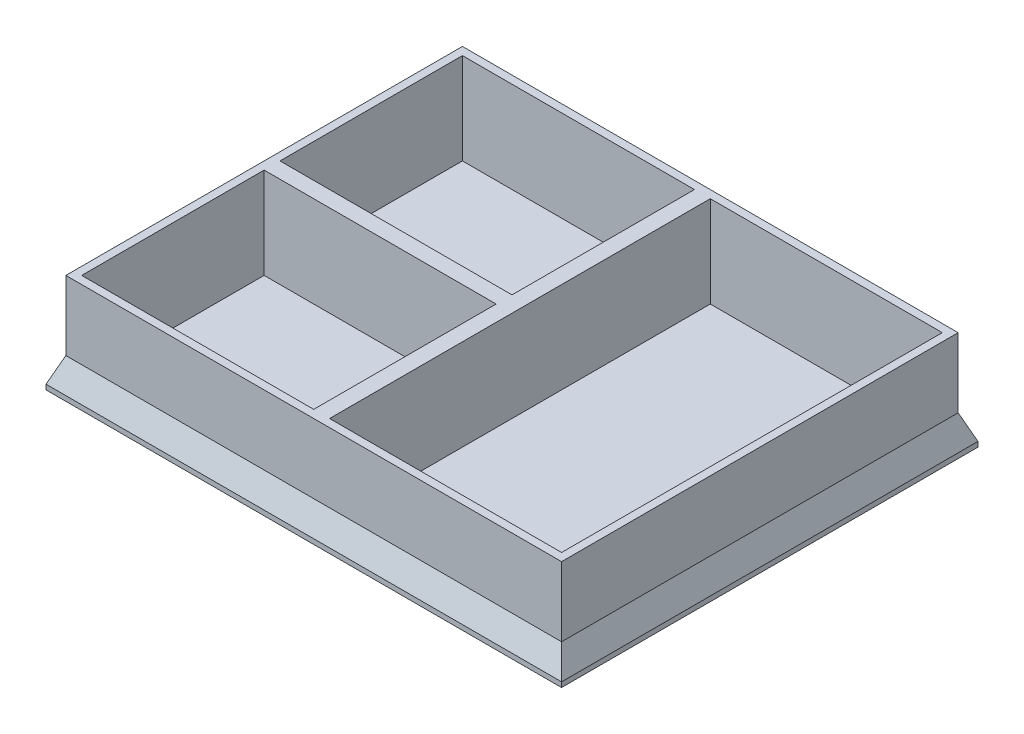
SolidWorks part; units mm, degrees
ref_plane "Přední rovina" through (0, 0, 0) normal (0, 0, 1) x (1, 0, 0)
ref_plane "Horní rovina" through (0, 0, 0) normal (0, 1, 0) x (1, 0, 0)
ref_plane "Pravá rovina" through (0, 0, 0) normal (1, 0, 0) x (0, 0, -1)
sketch "Skica1" plane through (0, 0, 0) normal (0, 1, 0) x (1, 0, 0)
  line L0 (0, 40) -> (0, -40) construction
  line L1 (-52, 42) -> (52, 42)
  line L2 (-52, 42) -> (-52, -42)
  line L3 (-52, -42) -> (52, -42)
  line L4 (52, 42) -> (52, -42)
  line L5 (-52, 42) -> (52, -42) construction
  line L6 (-52, -42) -> (52, 42) construction
  line L7 (-50, 40) -> (50, 40)
  line L8 (-50, 40) -> (-50, -40)
  line L9 (-50, -40) -> (50, -40)
  line L10 (50, 40) -> (50, -40)
  line L11 (-50, 40) -> (50, -40) construction
  line L12 (-50, -40) -> (50, 40) construction
  line L13 (-50, 0) -> (50, 0) construction
  line L14 (-50, 0) -> (0, 40) construction
  line L15 (-50, 40) -> (0, 0) construction
  line L16 (0, -40) -> (-50, 0) construction
  line L17 (-48.4, 38.4) -> (-1.6, 38.4)
  line L18 (-48.4, 38.4) -> (-48.4, 1.6)
  line L19 (-48.4, 1.6) -> (-1.6, 1.6)
  line L20 (-1.6, 38.4) -> (-1.6, 1.6)
  line L21 (-48.4, 38.4) -> (-1.6, 1.6) construction
  line L22 (-48.4, 1.6) -> (-1.6, 38.4) construction
  line L23 (-50, -40) -> (0, 0) construction
  line L24 (0, 40) -> (50, -40) construction
  line L25 (-48.4, -1.6) -> (-1.6, -1.6)
  line L26 (-48.4, -1.6) -> (-48.4, -38.4)
  line L27 (-48.4, -38.4) -> (-1.6, -38.4)
  line L28 (-1.6, -1.6) -> (-1.6, -38.4)
  line L29 (-48.4, -1.6) -> (-1.6, -38.4) construction
  line L30 (-48.4, -38.4) -> (-1.6, -1.6) construction
  line L31 (0, -40) -> (50, 40) construction
  line L33 (1.6, 38.4) -> (48.4, 38.4)
  line L34 (1.6, 38.4) -> (1.6, -38.4)
  line L35 (1.6, -38.4) -> (48.4, -38.4)
  line L36 (48.4, 38.4) -> (48.4, -38.4)
  line L37 (1.6, 38.4) -> (48.4, -38.4) construction
  line L38 (1.6, -38.4) -> (48.4, 38.4) construction
  point P0 (0, 0)
  point P1 (0, 0)
  point P2 (0, 0)
  point P16 (-25, 20)
  point P22 (-25, -20)
  point P27 (25, 0)
  dimension "D1" = 104
  dimension "D2" = 84
  dimension "D3" = 100
  dimension "D4" = 80
  dimension "D5" = 46.8
  dimension "D6" = 36.8
  dimension "D7" = 46.8
  dimension "D8" = 36.8
  dimension "D9" = 46.8
  dimension "D10" = 76.8
extrude "Přidat vysunutím1" add sketch "Skica1" along normal blind 20 contours L10 L7 L8 L9 L17 L20 L19 L18 L25 L28 L27 L26 L33 L36 L35 L34 region at (-3.8948, 0, 0)
extrude "Přidat vysunutím3" add sketch "Skica1<6>" along normal blind 1.6 contours L2 L3 L4 L1
sketch "Skica1<6>" plane through (0, 0, 0) normal (0, 1, 0) x (1, 0, 0) same geometry as "Skica1"
extrude "Přidat vysunutím4" add sketch "Skica1<7>" along normal blind 6 contours L4 L1 L2 L3 L7 L10 L9 L8 region at (0, 0, -40.6631)
sketch "Skica1<7>" plane through (0, 0, 0) normal (0, 1, 0) x (1, 0, 0) same geometry as "Skica1"
chamfer "Zkosení14" distance 2 distance2 5 4 edges at (0, 6, -42) (-52, 6, 0) (0, 6, 42) (52, 6, 0) first distance on face at (0, 6, 0)
